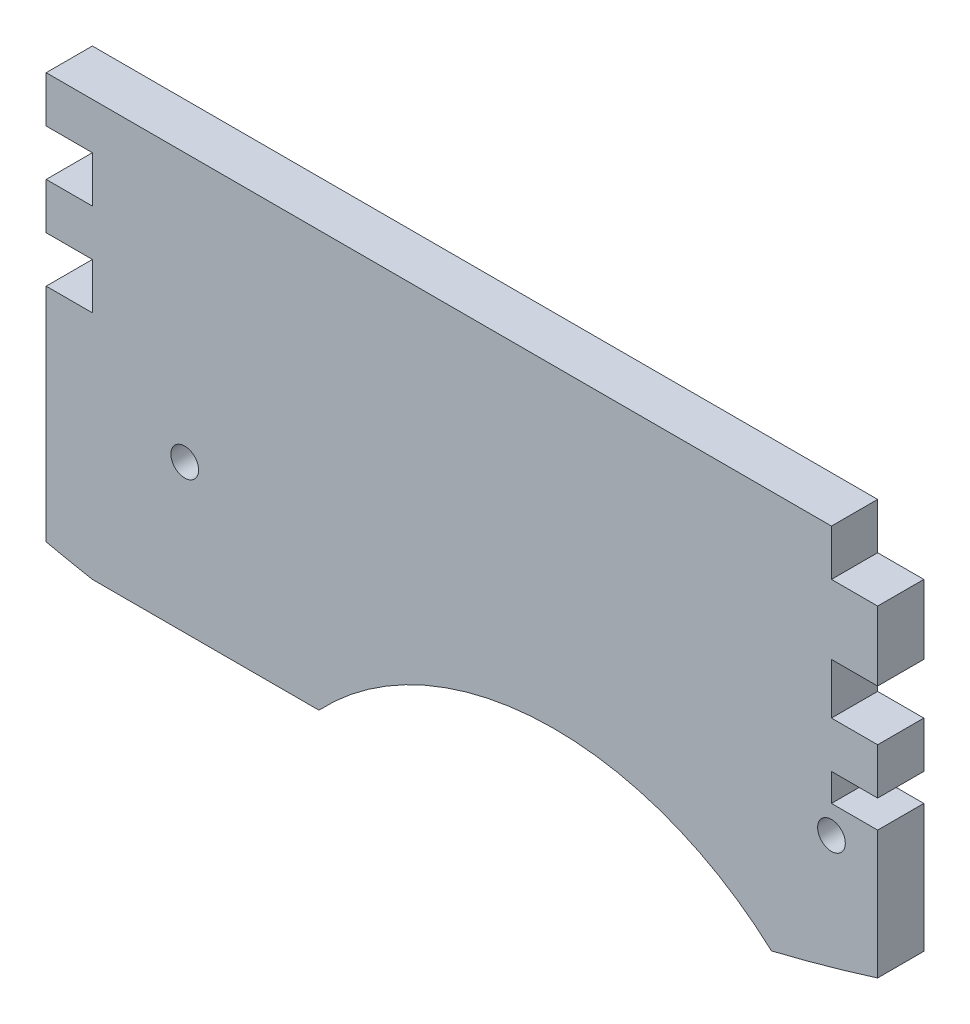
SolidWorks part; units mm, degrees
ref_plane "Plan de face" through (0, 0, 0) normal (0, 0, 1) x (1, 0, 0)
ref_plane "Plan de dessus" through (0, 0, 0) normal (0, 1, 0) x (1, 0, 0)
ref_plane "Plan de droite" through (0, 0, 0) normal (1, 0, 0) x (0, 0, -1)
sketch "Esquisse1" plane through (0, 0, 0) normal (0, 0, 1) x (1, 0, 0)
  line L0 (15, 67) -> (15, -4) construction
  line L1 (0, 0) -> (29.5245, 0)
  line L2 (0, 0) -> (0, 24.9897)
  line L4 (90, 0) -> (90, 19)
  line L5 (0, 39.9974) -> (0, 45)
  line L6 (85, 32.5) -> (90, 32.5)
  line L7 (85, 32.5) -> (85, 27)
  line L8 (85, 27) -> (90, 27)
  line L9 (90, 32.5) -> (90, 40)
  line L10 (15, 16) -> (85, 16) construction
  line L11 (80.4755, 0) -> (90, 0)
  line L12 (85, 22) -> (90, 22)
  line L13 (85, 22) -> (85, 19)
  line L14 (85, 19) -> (90, 19)
  line L16 (0, 39.9974) -> (5, 39.9974)
  line L17 (0, 29.9923) -> (0, 34.9949)
  line L18 (0, 34.9949) -> (5, 34.9949)
  line L19 (5, 39.9974) -> (5, 34.9949)
  line L20 (0, 29.9923) -> (5, 29.9923)
  line L21 (90, 22) -> (90, 27)
  line L22 (0, 24.9897) -> (5, 24.9897)
  line L23 (5, 29.9923) -> (5, 24.9897)
  line L24 (90, 40) -> (85, 40)
  line L26 (85, 45) -> (0, 45)
  line L27 (85, 40) -> (85, 45)
  circle A4 centre (15, 16) radius 1.5
  circle A5 centre (15, 16) radius 1.5 construction
  circle A6 centre (85, 16) radius 1.5
  circle A7 centre (55, -24) radius 35 construction
  arc A8 (29.5245, 0) -> (80.4755, 0) centre (55, -24) cw
  dimension "D6" = 19
  dimension "D8" = 5
  dimension "D9" = 3
  dimension "D10" = 70
  dimension "D13" = 70
  dimension "D16" = 90
  dimension "D2" = 15
  dimension "D3" = 5
  dimension "D4" = 16
  dimension "D5" = 7.5
  dimension "D7" = 5
  dimension "D11" = 3
  dimension "D12" = 5.5
  dimension "D14" = 40
  dimension "D15" = 40
  dimension "D17" = 5
  dimension "D18" = 5.0026
extrude "Boss.-Extru.1" add sketch "Esquisse1" along normal blind 5 contours L1 A8 L11 L4 A6 L14 L13 L12 L21 L8 L7 L6 L9 L5 L16 L19 L18 L17 L20 L23 L22 L2 A4 region at (43.6731, 24.1726, 0)
sketch "Esquisse2" plane through (0, 0, 5) normal (0, 0, 1) x (1, 0, 0)
  line L0 (0, 0) -> (29.5245, 0) construction
  line L1 (159.1841, 46.4587) -> (172.199, 38.2364)
  line L2 (-71.4456, 16.1728) -> (-46.9096, 18.5734)
  circle A0 centre (15, 16) radius 1.5 construction
  arc A1 (-46.9096, 18.5734) -> (159.1841, 46.4587) centre (37.2645, 172) ccw
  arc A2 (-71.4456, 16.1728) -> (172.199, 38.2364) centre (37.2645, 172) ccw
  point P0 (5, 0)
  dimension "D2" = 15
  dimension "D3" = 175
  dimension "D1" = 10
  dimension "D4" = 172
extrude "Enlèv. mat.-Extru.1" cut sketch "Esquisse2" against normal blind 10
